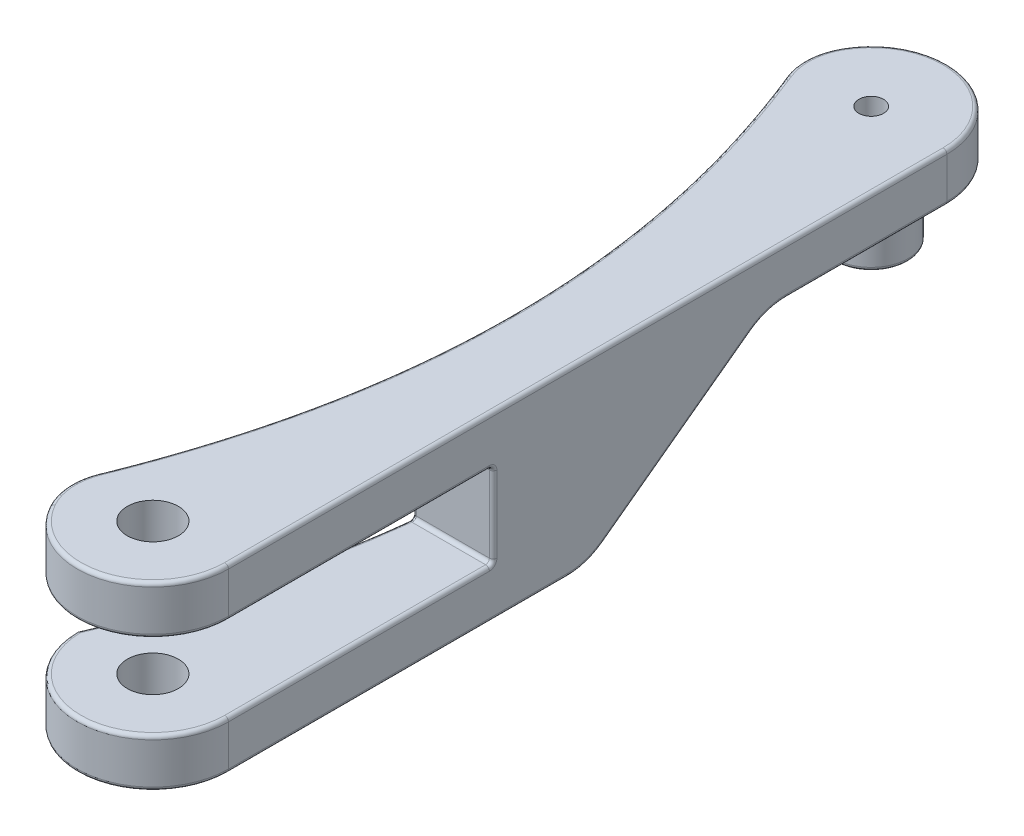
SolidWorks part; units mm, degrees
ref_plane "Front Plane" through (0, 0, 0) normal (0, 0, 1) x (1, 0, 0)
ref_plane "Top Plane" through (0, 0, 0) normal (0, 1, 0) x (1, 0, 0)
ref_plane "Right Plane" through (0, 0, 0) normal (1, 0, 0) x (0, 0, -1)
sketch "Sketch2" plane through (0, 0, 0) normal (0, 1, 0) x (1, 0, 0)
  line L0 (0, 0) -> (0, -95) construction
  line L1 (10, 0) -> (10, -95)
  line L2 (-10, 0) -> (-10, -95)
  arc A0 (10, 0) -> (-10, 0) centre (0, 0) ccw
  arc A1 (-10, -95) -> (10, -95) centre (0, -95) ccw
  circle A2 centre (0, 0) radius 1.625
  circle A3 centre (0, -95) radius 3.3782
  point P3 (0, -47.5)
  dimension "D2" = 20
  dimension "D3" = 3.25
  dimension "D4" = 6.7564
  dimension "D1" = 95
extrude "Boss-Extrude1" add sketch "Sketch2" along normal blind 16.5
sketch "Sketch3" plane through (0, 0, 0) normal (0, -1, 0) x (1, 0, 0)
  circle A0 centre (0, 0) radius 3.125
  dimension "D1" = 6.25
extrude "Cut-Extrude1" cut sketch "Sketch3" against normal blind 4.25
sketch "Sketch5" plane through (0, 0, 0) normal (0, -1, 0) x (1, 0, 0)
  line L0 (-10, 0) -> (-10, 47.5)
  line L1 (-10, 0) -> (-10, 95) construction
  line L2 (-10, 47.5) -> (10, 47.5)
  line L4 (10, 47.5) -> (10, 0)
  line L5 (10, 95) -> (10, 0) construction
  arc A0 (-10, 0) -> (10, 0) centre (0, 0) ccw
  arc A1 (-10, 0) -> (10, 0) centre (0, 0) ccw construction
  circle A2 centre (0, 0) radius 4.875
  dimension "D1" = 9.75
extrude "Cut-Extrude3" cut sketch "Sketch5" against normal blind 10.1
sketch "Sketch10" plane through (0, 0, 0) normal (0, -1, 0) x (1, 0, 0)
  line L0 (-10, 47.5) -> (10, 47.5)
  line L5 (-10, 47.5) -> (-10, 95)
  line L6 (10, 95) -> (10, 47.5)
  line L7 (-10, 47.5) -> (-10, 95)
  line L8 (10, 95) -> (10, 47.5)
  circle A1 centre (0, 95) radius 3.3782
  arc A2 (10, 95) -> (-10, 95) centre (0, 95) ccw
  arc A3 (10, 95) -> (-10, 95) centre (0, 95) ccw
  circle A4 centre (0, 95) radius 3.3782 construction
  dimension "D1" = 0
extrude "Boss-Extrude3" add sketch "Sketch10" along normal blind 7.4
sketch "Sketch8" plane through (10, 0, 0) normal (1, 0, 0) x (0, 0, -1)
  line L0 (-47.5, -7.4) -> (-23.75, 10.1)
  line L1 (0, 10.1) -> (-47.5, 10.1) construction
  line L2 (-23.75, 10.1) -> (-47.5, 10.1)
  line L3 (-47.5, 10.1) -> (-47.5, -7.4)
extrude "Boss-Extrude2" add sketch "Sketch8" against normal up to surface (20 mm away) up to face at (-10, 6.4, 47.5)
sketch "Sketch4" plane through (0, 16.5, 0) normal (0, 1, 0) x (1, 0, 0)
  line L0 (-10, 0) -> (-10, -95) construction
  line L1 (-10, 0) -> (-10, -95)
  spline S0 degree 2 poles (-10, 0) (10, -47.5) (-10, -95) knots 0 0 0 1 1 1
  point P8 (-10, -47.5)
extrude "Cut-Extrude2" cut sketch "Sketch4" against normal through all
sketch "Sketch9" plane through (0, 0, 0) normal (1, 0, 0) x (0, 0, -1)
  line L0 (-105, 16.5) -> (-105, -7.4) construction
  line L1 (-105, 10.1) -> (-60, 10.1)
  line L2 (-105, 10.1) -> (-105, -1)
  line L3 (-105, -1) -> (-60, -1)
  line L4 (-60, 10.1) -> (-60, -1)
  point P4 (-105, 4.55)
  dimension "D1" = 11.1
  dimension "D2" = 45
extrude "Cut-Extrude4" cut sketch "Sketch9" against normal through all both and the other way through all
sketch "Sketch13" plane through (0, 0, 0) normal (0, -1, 0) x (1, 0, 0)
  circle A0 centre (0, 0) radius 3.125 construction
  circle A1 centre (0, 0) radius 4.875
  circle A2 centre (0, 0) radius 4.875
  circle A3 centre (0, 0) radius 3.125
  dimension "D1" = 0
extrude "Cut-Extrude5" cut sketch "Sketch13" against normal blind 1
fillet "Fillet1" radius 8 4 edges at (-10, 13.3, 95) (3.75, 10.1, 23.75) (5, -7.4, 47.5)
fillet "Fillet2" radius 0.5 32 edges at (10, 4.55, 60) (10, 10.1, 77.5) (2.5098, 10.1, 104.6799) (-9.7326, 10.1, 96.4681) (-0.6925, 4.55, 60) (4.6537, 10.1, 60) (0, -1, 105) (10, -1, 77.5) (4.6537, -1, 60) (10, 1.35, 35.625) (10, 9.7001, 23.6186) (10, 10.1, 10.5605) (-9.7326, 10.1, -1.4681) (-2.4894, 9.6379, 23.8005) (-9.7326, 16.5, 96.4681) (2.5098, 16.5, 104.6799) (10, 16.5, 47.5) (2.5098, 16.5, -9.6799) (-9.7326, 16.5, -1.4681) (0, -7.4, 105) (10, -7.4, 72.5645) (10, -7.0001, 47.6314) (-0.0003, -7.0469, 47.7785) (0, 10.1, -4.875) (0, 1, -4.875)
ref_plane "Plane1" through (0, 8.25, 0) normal (0, 1, 0) x (1, 0, 0)
sketch "Sketch11" plane through (0, 16.5, 0) normal (0, 1, 0) x (1, 0, 0)
  circle A0 centre (0, 0) radius 3.125
  dimension "D1" = 6.25
ref_plane "Plane2" through (0, 14, 0) normal (0, 1, 0) x (1, 0, 0)
sketch "Sketch12" plane through (0, 14, 0) normal (0, 1, 0) x (1, 0, 0)
  circle A0 centre (0, 0) radius 1.625
  circle A1 centre (0, 0) radius 1.625
loft "Cut-Loft1" [suppressed] cut profiles "Sketch12", "Sketch11"
